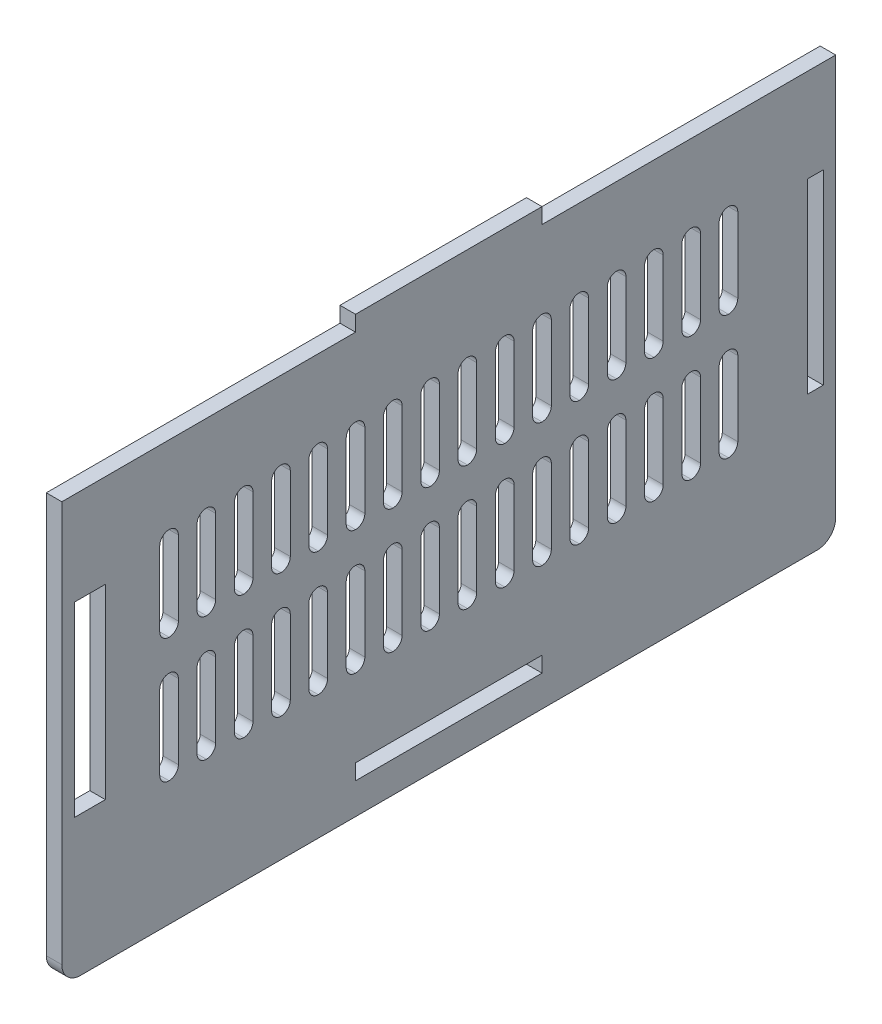
SolidWorks part; units mm, degrees
material "Maple"
ref_plane "Front Plane" through (0, 0, 0) normal (0, 0, 1) x (1, 0, 0)
ref_plane "Top Plane" through (0, 0, 0) normal (0, 1, 0) x (1, 0, 0)
ref_plane "Right Plane" through (0, 0, 0) normal (1, 0, 0) x (0, 0, -1)
sketch "Sketch1" plane through (0, 0, 0) normal (1, 0, 0) x (0, 0, -1)
  line L5 (-62.25, 30) -> (62.25, 30) construction
  line L6 (-62.25, -32.5) -> (62.25, -32.5) construction
  line L10 (-62.25, -32.5) -> (-62.25, 32.5) construction
  line L11 (-62.25, 32.5) -> (62.25, 32.5) construction
  line L12 (62.25, -32.5) -> (62.25, 32.5) construction
  line L13 (-62.25, -32.5) -> (62.25, 32.5) construction
  line L14 (-62.25, 32.5) -> (62.25, -32.5) construction
  line L15 (60.25, 30) -> (60.25, -32.5) construction
  line L16 (0, 32.5) -> (0, -32.5) construction
  line L17 (-62.25, 0) -> (62.25, 0) construction
  line L18 (-62.25, 30) -> (-15, 30)
  line L19 (-15, 30) -> (-15, 32.5)
  line L20 (-15, 32.5) -> (15, 32.5)
  line L21 (15, 30) -> (15, 32.5)
  line L22 (62.25, 30) -> (15, 30)
  line L23 (-62.25, 30) -> (-15, 30)
  line L24 (-15, 30) -> (-15, 32.5)
  line L25 (15, 30) -> (15, 32.5)
  line L26 (62.25, 30) -> (15, 30)
  line L27 (62.25, -30) -> (15, -30) construction
  line L28 (-15, -32.5) -> (15, -32.5) construction
  line L29 (-15, -30) -> (-15, -32.5)
  line L30 (15, -30) -> (15, -32.5)
  line L31 (-62.25, -30) -> (-15, -30) construction
  line L32 (-62.25, -30) -> (-15, -30) construction
  line L33 (-62.25, 30) -> (-62.25, -30)
  line L34 (62.25, 30) -> (62.25, -30)
  line L35 (-57.75, 15) -> (-60.25, 15)
  line L36 (57.75, -15) -> (60.25, -15)
  line L37 (57.75, -15) -> (57.75, 15)
  line L38 (57.75, 15) -> (60.25, 15)
  line L39 (60.25, -15) -> (60.25, 15)
  line L40 (57.75, -15) -> (60.25, 15) construction
  line L41 (57.75, 15) -> (60.25, -15) construction
  line L42 (-60.25, -15) -> (-60.25, 15)
  line L43 (-57.75, -15) -> (-60.25, -15)
  line L45 (-15, -30) -> (15, -30)
  line L46 (-57.75, 15) -> (-55.25, 15)
  line L47 (-57.75, 15) -> (-57.75, -15) construction
  line L48 (-57.75, -15) -> (-55.25, -15)
  line L49 (-55.25, 15) -> (-55.25, -15)
  line L50 (-15, -32.5) -> (15, -32.5) construction
  line L51 (-15, -32.5) -> (-15, -37.5) construction
  line L52 (-15, -37.5) -> (15, -37.5)
  line L53 (15, -32.5) -> (15, -37.5) construction
  line L54 (-62.25, -30) -> (-62.25, -37.5)
  line L55 (-62.25, -37.5) -> (-15, -37.5)
  line L56 (15, -37.5) -> (62.25, -37.5)
  line L57 (62.25, -37.5) -> (62.25, -30)
  line L58 (-15, -32.5) -> (15, -32.5)
  point P0 (0, 0)
  point P23 (59, 0)
  dimension "D1" = 2.5
  dimension "D2" = 2
  dimension "D3" = 65
  dimension "D4" = 124.5
  dimension "D5" = 30
  dimension "D6" = 2.5
  dimension "D7" = 5
extrude "Boss-Extrude1" add sketch "Sketch1" along normal mid plane 2.5 contours L34 L22 L21 L20 L19 L18 L33 L31 L29 L28 L30 L27 L43 L42 L35 L39 L36 L37 L38 region at (0, -3.28, -0.5181)
fillet "Fillet1" radius 3 2 edges at (0, -37.5, -62.25) (0, -37.5, 62.25)
sketch "Sketch2" plane through (1.25, 0, 0) normal (1, 0, 0) x (0, 0, -1)
  line L0 (-43.6352, 0) -> (45.3353, 0) construction
  line L5 (-46.5, 17.5) -> (-43.5, 17.5)
  line L6 (-46.5, 17.5) -> (-46.5, 2.5)
  line L7 (-46.5, 2.5) -> (-43.5, 2.5)
  line L8 (-43.5, 17.5) -> (-43.5, 2.5)
  line L9 (-46.5, 17.5) -> (-43.5, 2.5) construction
  line L10 (-46.5, 2.5) -> (-43.5, 17.5) construction
  line L11 (-46.5, -2.5) -> (-43.5, -2.5)
  line L12 (-43.5, -17.5) -> (-43.5, -2.5)
  line L13 (-46.5, -17.5) -> (-43.5, -17.5)
  line L14 (-46.5, -17.5) -> (-46.5, -2.5)
  line L15 (-40.5, 17.5) -> (-40.5, 2.5)
  line L16 (-40.5, 17.5) -> (-37.5, 17.5)
  line L17 (-37.5, 17.5) -> (-37.5, 2.5)
  line L18 (-40.5, 2.5) -> (-37.5, 2.5)
  line L19 (-40.5, -2.5) -> (-37.5, -2.5)
  line L20 (-37.5, -17.5) -> (-37.5, -2.5)
  line L21 (-40.5, -17.5) -> (-37.5, -17.5)
  line L22 (-40.5, -17.5) -> (-40.5, -2.5)
  line L23 (-34.5, 17.5) -> (-34.5, 2.5)
  line L24 (-34.5, 17.5) -> (-31.5, 17.5)
  line L25 (-31.5, 17.5) -> (-31.5, 2.5)
  line L26 (-34.5, 2.5) -> (-31.5, 2.5)
  line L27 (-34.5, -2.5) -> (-31.5, -2.5)
  line L28 (-31.5, -17.5) -> (-31.5, -2.5)
  line L29 (-34.5, -17.5) -> (-31.5, -17.5)
  line L30 (-34.5, -17.5) -> (-34.5, -2.5)
  line L31 (-28.5, 17.5) -> (-28.5, 2.5)
  line L32 (-28.5, 17.5) -> (-25.5, 17.5)
  line L33 (-25.5, 17.5) -> (-25.5, 2.5)
  line L34 (-28.5, 2.5) -> (-25.5, 2.5)
  line L35 (-28.5, -2.5) -> (-25.5, -2.5)
  line L36 (-25.5, -17.5) -> (-25.5, -2.5)
  line L37 (-28.5, -17.5) -> (-25.5, -17.5)
  line L38 (-28.5, -17.5) -> (-28.5, -2.5)
  line L39 (-22.5, 17.5) -> (-22.5, 2.5)
  line L40 (-22.5, 17.5) -> (-19.5, 17.5)
  line L41 (-19.5, 17.5) -> (-19.5, 2.5)
  line L42 (-22.5, 2.5) -> (-19.5, 2.5)
  line L43 (-22.5, -2.5) -> (-19.5, -2.5)
  line L44 (-19.5, -17.5) -> (-19.5, -2.5)
  line L45 (-22.5, -17.5) -> (-19.5, -17.5)
  line L46 (-22.5, -17.5) -> (-22.5, -2.5)
  line L47 (-16.5, 17.5) -> (-16.5, 2.5)
  line L48 (-16.5, 17.5) -> (-13.5, 17.5)
  line L49 (-13.5, 17.5) -> (-13.5, 2.5)
  line L50 (-16.5, 2.5) -> (-13.5, 2.5)
  line L51 (-16.5, -2.5) -> (-13.5, -2.5)
  line L52 (-13.5, -17.5) -> (-13.5, -2.5)
  line L53 (-16.5, -17.5) -> (-13.5, -17.5)
  line L54 (-16.5, -17.5) -> (-16.5, -2.5)
  line L55 (-10.5, 17.5) -> (-10.5, 2.5)
  line L56 (-10.5, 17.5) -> (-7.5, 17.5)
  line L57 (-7.5, 17.5) -> (-7.5, 2.5)
  line L58 (-10.5, 2.5) -> (-7.5, 2.5)
  line L59 (-10.5, -2.5) -> (-7.5, -2.5)
  line L60 (-7.5, -17.5) -> (-7.5, -2.5)
  line L61 (-10.5, -17.5) -> (-7.5, -17.5)
  line L62 (-10.5, -17.5) -> (-10.5, -2.5)
  line L63 (-4.5, 17.5) -> (-4.5, 2.5)
  line L64 (-4.5, 17.5) -> (-1.5, 17.5)
  line L65 (-1.5, 17.5) -> (-1.5, 2.5)
  line L66 (-4.5, 2.5) -> (-1.5, 2.5)
  line L67 (-4.5, -2.5) -> (-1.5, -2.5)
  line L68 (-1.5, -17.5) -> (-1.5, -2.5)
  line L69 (-4.5, -17.5) -> (-1.5, -17.5)
  line L70 (-4.5, -17.5) -> (-4.5, -2.5)
  line L71 (0, 15.6682) -> (0, -14.1422) construction
  line L72 (46.5, 2.5) -> (43.5, 17.5) construction
  line L73 (46.5, 17.5) -> (43.5, 2.5) construction
  line L74 (4.5, -17.5) -> (4.5, -2.5)
  line L75 (4.5, -17.5) -> (1.5, -17.5)
  line L76 (1.5, -17.5) -> (1.5, -2.5)
  line L77 (4.5, -2.5) -> (1.5, -2.5)
  line L78 (4.5, 2.5) -> (1.5, 2.5)
  line L79 (1.5, 17.5) -> (1.5, 2.5)
  line L80 (4.5, 17.5) -> (1.5, 17.5)
  line L81 (4.5, 17.5) -> (4.5, 2.5)
  line L82 (10.5, -17.5) -> (10.5, -2.5)
  line L83 (10.5, -17.5) -> (7.5, -17.5)
  line L84 (7.5, -17.5) -> (7.5, -2.5)
  line L85 (10.5, -2.5) -> (7.5, -2.5)
  line L86 (10.5, 2.5) -> (7.5, 2.5)
  line L87 (7.5, 17.5) -> (7.5, 2.5)
  line L88 (10.5, 17.5) -> (7.5, 17.5)
  line L89 (10.5, 17.5) -> (10.5, 2.5)
  line L90 (16.5, -17.5) -> (16.5, -2.5)
  line L91 (16.5, -17.5) -> (13.5, -17.5)
  line L92 (13.5, -17.5) -> (13.5, -2.5)
  line L93 (16.5, -2.5) -> (13.5, -2.5)
  line L94 (16.5, 2.5) -> (13.5, 2.5)
  line L95 (13.5, 17.5) -> (13.5, 2.5)
  line L96 (16.5, 17.5) -> (13.5, 17.5)
  line L97 (16.5, 17.5) -> (16.5, 2.5)
  line L98 (22.5, -17.5) -> (22.5, -2.5)
  line L99 (22.5, -17.5) -> (19.5, -17.5)
  line L100 (19.5, -17.5) -> (19.5, -2.5)
  line L101 (22.5, -2.5) -> (19.5, -2.5)
  line L102 (22.5, 2.5) -> (19.5, 2.5)
  line L103 (19.5, 17.5) -> (19.5, 2.5)
  line L104 (22.5, 17.5) -> (19.5, 17.5)
  line L105 (22.5, 17.5) -> (22.5, 2.5)
  line L106 (28.5, -17.5) -> (28.5, -2.5)
  line L107 (28.5, -17.5) -> (25.5, -17.5)
  line L108 (25.5, -17.5) -> (25.5, -2.5)
  line L109 (28.5, -2.5) -> (25.5, -2.5)
  line L110 (28.5, 2.5) -> (25.5, 2.5)
  line L111 (25.5, 17.5) -> (25.5, 2.5)
  line L112 (28.5, 17.5) -> (25.5, 17.5)
  line L113 (28.5, 17.5) -> (28.5, 2.5)
  line L114 (34.5, -17.5) -> (34.5, -2.5)
  line L115 (34.5, -17.5) -> (31.5, -17.5)
  line L116 (31.5, -17.5) -> (31.5, -2.5)
  line L117 (34.5, -2.5) -> (31.5, -2.5)
  line L118 (34.5, 2.5) -> (31.5, 2.5)
  line L119 (31.5, 17.5) -> (31.5, 2.5)
  line L120 (34.5, 17.5) -> (31.5, 17.5)
  line L121 (34.5, 17.5) -> (34.5, 2.5)
  line L122 (40.5, -17.5) -> (40.5, -2.5)
  line L123 (40.5, -17.5) -> (37.5, -17.5)
  line L124 (37.5, -17.5) -> (37.5, -2.5)
  line L125 (40.5, -2.5) -> (37.5, -2.5)
  line L126 (40.5, 2.5) -> (37.5, 2.5)
  line L127 (37.5, 17.5) -> (37.5, 2.5)
  line L128 (40.5, 17.5) -> (37.5, 17.5)
  line L129 (40.5, 17.5) -> (40.5, 2.5)
  line L130 (46.5, -17.5) -> (46.5, -2.5)
  line L131 (46.5, -17.5) -> (43.5, -17.5)
  line L132 (43.5, -17.5) -> (43.5, -2.5)
  line L133 (46.5, -2.5) -> (43.5, -2.5)
  line L134 (43.5, 17.5) -> (43.5, 2.5)
  line L135 (46.5, 2.5) -> (43.5, 2.5)
  line L136 (46.5, 17.5) -> (46.5, 2.5)
  line L137 (46.5, 17.5) -> (43.5, 17.5)
  point P0 (-45, 10)
  point P135 (45, 10)
  dimension "D1" = 15
  dimension "D2" = 3
  dimension "D3" = 5
  dimension "D5" = 3
  dimension "D6" = 3
  dimension "D4" = 8
extrude "Cut-Extrude1" cut sketch "Sketch2" against normal through all
fillet "Fillet2" radius 1.5 128 edges at (0, -17.5, -46.5) (0, -2.5, -46.5) (0, -2.5, -43.5) (0, -17.5, -43.5) (0, 17.5, -40.5) (0, 17.5, -37.5) (0, 2.5, -37.5) (0, 2.5, -40.5) (0, -17.5, -40.5) (0, -2.5, -40.5) (0, -2.5, -37.5) (0, -17.5, -37.5) (0, 17.5, -34.5) (0, 17.5, -31.5) (0, 2.5, -31.5) (0, 2.5, -34.5) (0, -17.5, -34.5) (0, -2.5, -34.5) (0, -2.5, -31.5) (0, -17.5, -31.5) (0, 17.5, -28.5) (0, 17.5, -25.5) (0, 2.5, -25.5) (0, 2.5, -28.5) (0, -17.5, -28.5) (0, -2.5, -28.5) (0, -2.5, -25.5) (0, -17.5, -25.5) (0, 17.5, -22.5) (0, 17.5, -19.5) (0, 2.5, -19.5) (0, 2.5, -22.5) (0, -17.5, -22.5) (0, -2.5, -22.5) (0, -2.5, -19.5) (0, -17.5, -19.5) (0, 17.5, -16.5) (0, 17.5, -13.5) (0, 2.5, -13.5) (0, 2.5, -16.5) (0, -17.5, -16.5) (0, -2.5, -16.5) (0, -2.5, -13.5) (0, -17.5, -13.5) (0, 17.5, -10.5) (0, 17.5, -7.5) (0, 2.5, -7.5) (0, 2.5, -10.5) (0, -17.5, -10.5) (0, -2.5, -10.5) (0, -2.5, -7.5) (0, -17.5, -7.5) (0, 17.5, -4.5) (0, 17.5, -1.5) (0, 2.5, -1.5) (0, 2.5, -4.5) (0, -17.5, -4.5) (0, -2.5, -4.5) (0, -2.5, -1.5) (0, -17.5, -1.5) (0, 17.5, -46.5) (0, 17.5, -43.5) (0, 2.5, -43.5) (0, 2.5, -46.5) (0, -17.5, 4.5) (0, -17.5, 1.5) (0, -2.5, 1.5) (0, -2.5, 4.5) (0, 2.5, 1.5) (0, 17.5, 1.5) (0, 17.5, 4.5) (0, 2.5, 4.5) (0, -17.5, 10.5) (0, -17.5, 7.5) (0, -2.5, 7.5) (0, -2.5, 10.5) (0, 2.5, 7.5) (0, 17.5, 7.5) (0, 17.5, 10.5) (0, 2.5, 10.5) (0, -17.5, 16.5) (0, -17.5, 13.5) (0, -2.5, 13.5) (0, -2.5, 16.5) (0, 2.5, 13.5) (0, 17.5, 13.5) (0, 17.5, 16.5) (0, 2.5, 16.5) (0, -17.5, 22.5) (0, -17.5, 19.5) (0, -2.5, 19.5) (0, -2.5, 22.5) (0, 2.5, 19.5) (0, 17.5, 19.5) (0, 17.5, 22.5) (0, 2.5, 22.5) (0, -17.5, 28.5) (0, -17.5, 25.5) (0, -2.5, 25.5) (0, -2.5, 28.5) (0, 2.5, 25.5) (0, 17.5, 25.5) (0, 17.5, 28.5) (0, 2.5, 28.5) (0, -17.5, 34.5) (0, -17.5, 31.5) (0, -2.5, 31.5) (0, -2.5, 34.5) (0, 2.5, 31.5) (0, 17.5, 31.5) (0, 17.5, 34.5) (0, 2.5, 34.5) (0, -17.5, 40.5) (0, -17.5, 37.5) (0, -2.5, 37.5) (0, -2.5, 40.5) (0, 2.5, 37.5) (0, 17.5, 37.5) (0, 17.5, 40.5) (0, 2.5, 40.5) (0, -17.5, 46.5) (0, -17.5, 43.5) (0, -2.5, 43.5) (0, -2.5, 46.5) (0, 17.5, 43.5) (0, 2.5, 46.5) (0, 2.5, 43.5) (0, 17.5, 46.5)
